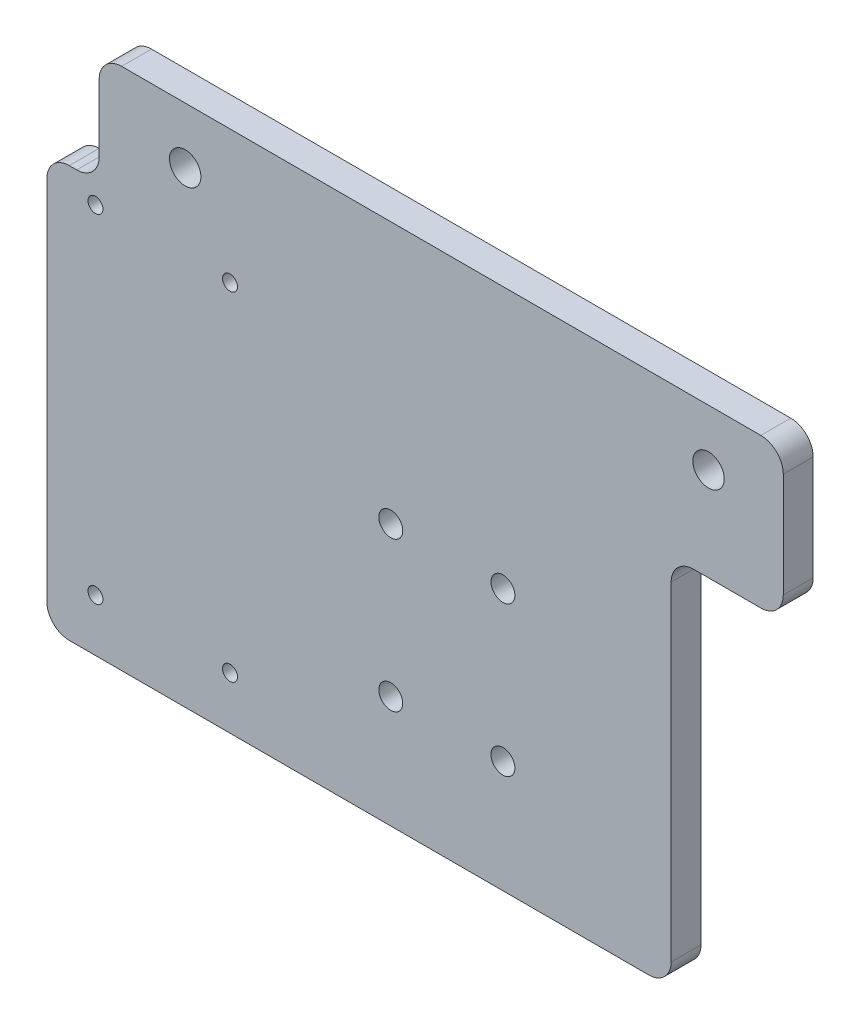
SolidWorks part; units mm, degrees
material "默认 (3)"
ref_plane "前视基准面" through (0, 0, 0) normal (0, 0, 1) x (1, 0, 0)
ref_plane "上视基准面" through (0, 0, 0) normal (0, 1, 0) x (1, 0, 0)
ref_plane "右视基准面" through (0, 0, 0) normal (1, 0, 0) x (0, 0, -1)
other "Configuration Table"
sketch "草图1" plane through (0, 0, 0) normal (0, 0, 1) x (1, 0, 0)
  line L0 (0, 0) -> (0, -50000) construction
  line L1 (-125, 15) -> (125, 15)
  line L2 (-125, 15) -> (-125, -15)
  line L3 (-125, -15) -> (125, -15)
  line L4 (125, 15) -> (125, -15)
  line L5 (-125, 15) -> (125, -15) construction
  line L6 (-125, -15) -> (125, 15) construction
  line L7 (-115, -10) -> (-115, 10) construction
  circle A0 centre (-115, -10) radius 1.5
  circle A1 centre (-115, 10) radius 1.5
  circle A2 centre (115, 10) radius 1.5
  circle A3 centre (115, -10) radius 1.5
  point P0 (0, 0)
  dimension "D6" = 5
  dimension "D7" = 3
  dimension "D1" = 250
  dimension "D2" = 30
  dimension "D4" = 20
  dimension "D5" = 10
  dimension "D3" = 2
extrude "凸台-拉伸1" add sketch "草图1" along normal blind 4
sketch "草图2" plane through (0, 0, 4) normal (0, 0, 1) x (1, 0, 0)
  line L0 (0, 0) -> (0, -50000) construction
  line L1 (0, 9) -> (50000, 9) construction
  line L2 (-23, 2.5) -> (23, 2.5) construction
  line L3 (-23, 2.5) -> (-23, 15.5) construction
  line L4 (-125, -15) -> (125, -15) construction
  circle A0 centre (-23, 2.5) radius 3
  circle A1 centre (23, 2.5) radius 3
  circle A2 centre (23, 15.5) radius 3
  circle A3 centre (-23, 15.5) radius 3
  dimension "D5" = 6
  dimension "D3" = 46
  dimension "D4" = 13
  dimension "D6" = 24
  dimension "D1" = 2
  dimension "D2" = 2
extrude "切除-拉伸1" cut sketch "草图2" against normal through all
sketch "草图3" plane through (0, 0, 4) normal (0, 0, 1) x (1, 0, 0)
  line L0 (0, 54.5) -> (0, -49945.5) construction
  line L1 (-125, 85) -> (125, 85)
  line L2 (-125, 85) -> (-125, 15)
  line L3 (-125, 15) -> (125, 15)
  line L4 (125, 85) -> (125, 15)
  line L5 (-125, 85) -> (125, 15) construction
  line L6 (-125, 15) -> (125, 85) construction
  line L8 (-115, 10) -> (-115, 30) construction
  circle A4 centre (-115, 10) radius 1.5 construction
  circle A5 centre (-115, 10) radius 1.5
  circle A6 centre (-115, 30) radius 1.5
  circle A7 centre (-115, 50) radius 1.5
  circle A8 centre (-115, 70) radius 1.5
  circle A9 centre (-115, 90) radius 1.5
  circle A10 centre (115, 10) radius 1.5
  circle A11 centre (115, 30) radius 1.5
  circle A12 centre (115, 50) radius 1.5
  circle A13 centre (115, 70) radius 1.5
  circle A14 centre (-35, 77.5) radius 2.1
  circle A15 centre (35, 77.5) radius 2.1
  point P0 (0, 50)
  line M16 (125, 15) -> (25.958, 15)
  dimension "D4" = 70
  dimension "D2" = 4.2
  dimension "D3" = 7.5
  dimension "D1" = 70
  dimension "D7" = 20
  dimension "D6" = 5
extrude "凸台-拉伸2" add sketch "草图3" against normal blind 4 contours L4 L1 L2 A12 A14 A6 A7 A8 A11 A13 M16 region at (0, 49.9563, 4)
sketch "草图4" plane through (0, 0, 4) normal (0, 0, 1) x (1, 0, 0)
  line L1 (-125, 85) -> (125, 85) construction
  line L8 (-125, -15) -> (125, -15) construction
  line L9 (-97, 70) -> (-48, 70)
  line L10 (-100, 67) -> (-100, 3)
  line L11 (-97, 0) -> (-48, 0)
  line L12 (-45, 67) -> (-45, 3)
  line L13 (-100, 70) -> (-45, 0) construction
  line L14 (-100, 0) -> (-45, 70) construction
  line L15 (-125, 85) -> (-125, -15) construction
  line L16 (97, 0) -> (48, 0)
  line L17 (45, 67) -> (45, 3)
  line L18 (97, 70) -> (48, 70)
  line L19 (100, 67) -> (100, 3)
  arc A4 (-48, 0) -> (-45, 3) centre (-48, 3) ccw
  arc A5 (-100, 3) -> (-97, 0) centre (-97, 3) ccw
  arc A6 (-48, 70) -> (-45, 67) centre (-48, 67) cw
  arc A7 (-97, 70) -> (-100, 67) centre (-97, 67) ccw
  arc A8 (48, 0) -> (45, 3) centre (48, 3) cw
  arc A9 (48, 70) -> (45, 67) centre (48, 67) ccw
  arc A10 (100, 3) -> (97, 0) centre (97, 3) cw
  arc A11 (97, 70) -> (100, 67) centre (97, 67) cw
  point P10 (-72.5, 35)
  dimension "D4" = 15
  dimension "D5" = 15
  dimension "D6" = 25
  dimension "D7" = 55
extrude "切除-拉伸2" cut sketch "草图4" against normal through all
fillet "圆角1" radius 5 4 edges at (125, -15, 2) (125, 85, 2) (-125, -15, 2) (-125, 85, 2)
sketch "草图5" plane through (0, 0, 4) normal (0, 0, 1) x (1, 0, 0)
  circle A0 centre (-23, 15.5) radius 3
  circle A1 centre (23, 15.5) radius 3
  dimension "D1" = 6
extrude "切除-拉伸3" cut sketch "草图5" against normal through all
sketch "草图8" plane through (0, 0, 4) normal (0, 0, 1) x (1, 0, 0)
  line L0 (-48, 70) -> (-97, 70) construction
  line L1 (-45, 70) -> (-65, 70)
  line L2 (-45, 70) -> (-45, 20)
  line L3 (-45, 20) -> (-65, 20)
  line L4 (-65, 70) -> (-65, 20)
  line L5 (-45, 3) -> (-45, 67) construction
  dimension "D1" = 50
  dimension "D2" = 20
extrude "凸台-拉伸4" add sketch "草图8" against normal up to surface (4 mm away) up to face at (-72.5, 35, 0)
sketch "草图9" plane through (0, 0, 4) normal (0, 0, 1) x (1, 0, 0)
  line L0 (-65, 20) -> (-45, 20) construction
  line L1 (-65, 70) -> (-65, 20) construction
  circle A0 centre (-47, 22) radius 1
  circle A1 centre (-29, 22) radius 1
  circle A2 centre (-47, 67.2) radius 1
  circle A3 centre (-29, 67.2) radius 1
  dimension "D1" = 2
  dimension "D4" = 2
  dimension "D5" = 18
  dimension "D2" = 2
  dimension "D3" = 2
extrude "切除-拉伸4" cut sketch "草图9" against normal blind 10
fillet "圆角3" [suppressed] radius 3
sketch "草图10" plane through (0, 0, 4) normal (0, 0, 1) x (1, 0, 0)
  line L0 (0, 0) -> (0, 130.9934) construction
  line L1 (35, 15) -> (35, -15)
  line L2 (35, 15) -> (-35, 15)
  line L3 (0, 15) -> (0, -15)
  line L4 (35, -15) -> (-35, -15)
  line L5 (-35, 15) -> (-35, -15)
  line L6 (-120, -15) -> (120, -15) construction
  dimension "D1" = 70
  dimension "D2" = 30
  dimension "D3" = 30
extrude "切除-拉伸5" cut sketch "草图10" against normal blind 10 contours L2 L5 L4 L3 | L4 L1 L2 L3 region at (17.5, 0, 4) region at (-17.5, 0, 4)
sketch "草图11" plane through (0, 0, 4) normal (0, 0, 1) x (1, 0, 0)
  line L1 (-35, 15) -> (35, 15)
  line L2 (-35, 15) -> (-35, 19.6041)
  line L3 (-35, 19.6041) -> (35, 19.6041)
  line L4 (35, 15) -> (35, 19.6041)
extrude "凸台-拉伸5" add sketch "草图11" against normal up to surface (4 mm away) up to face at (-28, 22, 0)
fillet "圆角4" radius 10 4 edges at (35, 15, 2) (35, -15, 2) (-35, -15, 2) (-35, 15, 2)
sketch "草图12" plane through (0, 0, 4) normal (0, 0, 1) x (1, 0, 0)
  line L0 (0, 85) -> (0, -53.6278) construction
  line L1 (-120, 85) -> (120, 85) construction
  line L2 (-159.4821, 67) -> (-159.4821, 15)
  line L3 (45, 67) -> (144.5907, 67)
  line L4 (45, 67) -> (45, 102.3315)
  line L5 (45, 102.3315) -> (144.5907, 102.3315)
  line L6 (144.5907, 67) -> (144.5907, 102.3315)
  line L7 (45, 67) -> (137.7054, 67)
  line L8 (45, 67) -> (45, 15)
  line L11 (25, 15) -> (159.4821, 15)
  line L12 (25, 15) -> (25, -21.4432)
  line L13 (25, -21.4432) -> (159.4821, -21.4432)
  line L14 (159.4821, 15) -> (159.4821, -21.4432)
  line L15 (45, 67) -> (159.4821, 67)
  line L16 (45, 67) -> (45, 15)
  line L17 (45, 15) -> (159.4821, 15)
  line L18 (159.4821, 67) -> (159.4821, 15)
  line L19 (-45, 15) -> (-159.4821, 15)
  line L20 (-56.5072, 67) -> (-56.5072, 15)
  line L21 (-56.5072, 67) -> (-159.4821, 67)
  line L22 (-159.4821, 15) -> (-159.4821, -21.4432)
  line L23 (-25, -21.4432) -> (-159.4821, -21.4432)
  line L24 (-25, 15) -> (-25, -21.4432)
  line L25 (-25, 15) -> (-159.4821, 15)
  line L26 (-56.5072, 67) -> (-56.5072, 102.3315)
  line L27 (-56.5072, 67) -> (-137.7054, 67)
  line L28 (-144.5907, 67) -> (-144.5907, 102.3315)
  line L29 (-56.5072, 102.3315) -> (-144.5907, 102.3315)
  line L31 (-56.5072, 67) -> (-144.5907, 67)
  line M33 (35, 5) -> (35, -5)
  arc M34 (35, -5) -> (45, -15) centre (45, -5) ccw
  line M35 (45, -15) -> (120, -15)
  arc M36 (120, -15) -> (125, -10) centre (120, -10) ccw
  line M37 (125, -10) -> (125, 80)
  arc M38 (125, 80) -> (120, 85) centre (120, 80) ccw
  line M39 (120, 85) -> (-120, 85)
  arc M40 (-120, 85) -> (-125, 80) centre (-120, 80) ccw
  line M41 (-125, 80) -> (-125, -10)
  arc M42 (-125, -10) -> (-120, -15) centre (-120, -10) ccw
  line M43 (-120, -15) -> (-45, -15)
  arc M44 (-45, -15) -> (-35, -5) centre (-45, -5) ccw
  line M45 (-35, -5) -> (-35, 5)
  arc M46 (-35, 5) -> (-25, 15) centre (-25, 5) cw
  arc M48 (25, 15) -> (35, 5) centre (25, 5) cw
  line M53 (-97, 70) -> (-65, 70)
  line M54 (-65, 70) -> (-65, 20)
  line M55 (-65, 20) -> (-45, 20)
  line M56 (-45, 20) -> (-45, 3)
  arc M57 (-45, 3) -> (-48, 0) centre (-48, 3) cw
  line M58 (-48, 0) -> (-97, 0)
  arc M59 (-97, 0) -> (-100, 3) centre (-97, 3) cw
  line M60 (-100, 3) -> (-100, 67)
  arc M61 (-100, 67) -> (-97, 70) centre (-97, 67) cw
  arc M62 (48, 0) -> (45, 3) centre (48, 3) cw
  line M63 (45, 3) -> (45, 67)
  arc M64 (45, 67) -> (48, 70) centre (48, 67) cw
  line M65 (48, 70) -> (97, 70)
  arc M66 (97, 70) -> (100, 67) centre (97, 67) cw
  line M67 (100, 67) -> (100, 3)
  arc M68 (100, 3) -> (97, 0) centre (97, 3) cw
  line M69 (97, 0) -> (48, 0)
  circle M70 centre (115, 10) radius 1.5
  circle M71 centre (-115, -10) radius 1.5
  circle M72 centre (-115, 10) radius 1.5
  circle M73 centre (115, -10) radius 1.5
  circle M74 centre (115, 70) radius 1.5
  circle M75 centre (115, 30) radius 1.5
  circle M76 centre (-115, 70) radius 1.5
  circle M77 centre (-115, 50) radius 1.5
  circle M78 centre (-115, 30) radius 1.5
  circle M79 centre (115, 50) radius 1.5
extrude "切除-拉伸6" cut sketch "草图12" against normal blind 10 contours L21 L29 L28 | L24 L25 L19 L22 L23 | L3 L6 L5 L4 | L18 L15 L3 L8 L11 | L14 L11 L12 L13 | L21 L19 L20 M54 M60 M55 | L21 L2 L19 M41 | L21 L19 M60 M41 M77 M78 | L20 L21 M54 M55 | L21 L26 M39 M40 M41 M61 M53 M54 M76 | L19 M56 M60 M59 M58 M57 | L25 L19 M46 M56 M57 M58 M59 M60 M41 M42 M43 M44 M45 M71 M72 | L11 M63 M62 M69 M68 M67 | L11 M48 M33 M34 M35 M36 M37 M67 M68 M69 M62 M63 M73 M70 | L11 L3 M67 M37 M79 M75 | L4 L3 M64 M65 M66 M37 M38 M39 M74 | L11 L3 M63 M67 | L3 M64 M66 M65 region at (-142.241, 41, 4) region at (101.6384, 90.6515, 4) region at (86.2583, 76.9569, 4) region at (-142.241, 13.6067, 4) region at (-107.0232, 90.3325, 4) region at (-112.4725, 41.011, 4) region at (-82.8679, -2.9916, 4) region at (-82.0042, 40.4642, 4) region at (-72.5, 7.5321, 4) region at (-91.2315, 76.6934, 4) region at (-60.7536, 43.5, 4) region at (72.5, 68.4801, 4) region at (72.5, 41, 4) region at (112.4725, 41.011, 4) region at (82.8679, -2.9916, 4) region at (72.5, 7.5321, 4) region at (142.241, 41, 4) region at (31.0858, 11.0858, 4)
fillet "圆角5" [suppressed] radius 2
sketch "草图14" plane through (0, 0, 4) normal (0, 0, 1) x (1, 0, 0)
  line L0 (45, 15) -> (-45, 15) construction
  line L1 (-45, 20) -> (-56.5072, 20)
  line L2 (-45, 20) -> (-45, 15)
  line L3 (-45, 15) -> (-56.5072, 15)
  line L4 (-56.5072, 20) -> (-56.5072, 15)
  line L5 (-56.5072, 85) -> (-56.5072, 20) construction
extrude "凸台-拉伸6" add sketch "草图14" against normal up to surface (4 mm away) up to face at (-28, 22, 0)
sketch "草图15" plane through (0, 0, 4) normal (0, 0, 1) x (1, 0, 0)
  line L0 (-56.5072, 85) -> (45, 85) construction
  line L1 (45, 15) -> (30, 15)
  line L2 (45, 15) -> (45, 65)
  line L3 (45, 65) -> (30, 65)
  line L4 (30, 15) -> (30, 65)
  line L5 (-56.5072, 15) -> (-53.5072, 15)
  line L6 (-56.5072, 15) -> (-56.5072, 70)
  line L7 (-56.5072, 70) -> (-53.5072, 70)
  line L8 (-53.5072, 15) -> (-53.5072, 70)
  line L9 (-56.5072, 70) -> (-46.5072, 70)
  line L10 (-56.5072, 70) -> (-56.5072, 85)
  line L11 (-56.5072, 85) -> (-46.5072, 85)
  line L12 (-46.5072, 70) -> (-46.5072, 85)
  line M11 (45, 85) -> (-56.5072, 85)
  line M12 (-56.5072, 85) -> (-56.5072, 15)
  line M13 (-56.5072, 15) -> (45, 15)
  line M14 (45, 15) -> (45, 85)
  dimension "D1" = 50
  dimension "D2" = 15
  dimension "D3" = 55
  dimension "D4" = 3
  dimension "D5" = 10
extrude "切除-拉伸7" cut sketch "草图15" against normal blind 10 contours L9 L12 L7 M11 M12 | L8 L7 M13 M12 | L4 L3 M13 M14 region at (37.5, 40, 4) region at (-55.0072, 42.5, 4) region at (-51.5072, 77.5, 4)
fillet "圆角6" radius 3 8 edges at (-53.5072, 70, 2) (-46.5072, 70, 2) (-46.5072, 85, 2) (45, 85, 2) (45, 65, 2) (30, 65, 2) (-53.5072, 15, 2) (30, 15, 2)
sketch "草图16" plane through (0, 0, 4) normal (0, 0, 1) x (1, 0, 0)
  line L0 (-35, 77.5) -> (35, 77.5)
  line L1 (0, 77.5) -> (0, -5.4389) construction
  line L2 (-43.5072, 85) -> (42, 85) construction
  line L3 (0, 57.5) -> (0, -25.4389) construction
  circle A0 centre (-7.5, 50) radius 1.6
  circle A1 centre (7.5, 50) radius 1.6
  circle A2 centre (-7.5, 30) radius 1.6
  circle A3 centre (7.5, 30) radius 1.6
  point P13 (0, 0)
  dimension "D1" = 3.2
  dimension "D2" = 15
  dimension "D3" = 35
  dimension "D5" = 20
  dimension "D4" = 2
extrude "切除-拉伸8" cut sketch "草图16" against normal blind 10 contours A0 | A1 | A2 | A3 region at (-7.5, 50, 4) region at (7.5, 50, 4) region at (-7.5, 30, 4) region at (7.5, 30, 4)
chamfer "倒角2" distance 1 angle 45 1 edges at (-5.9, 50, 0)
